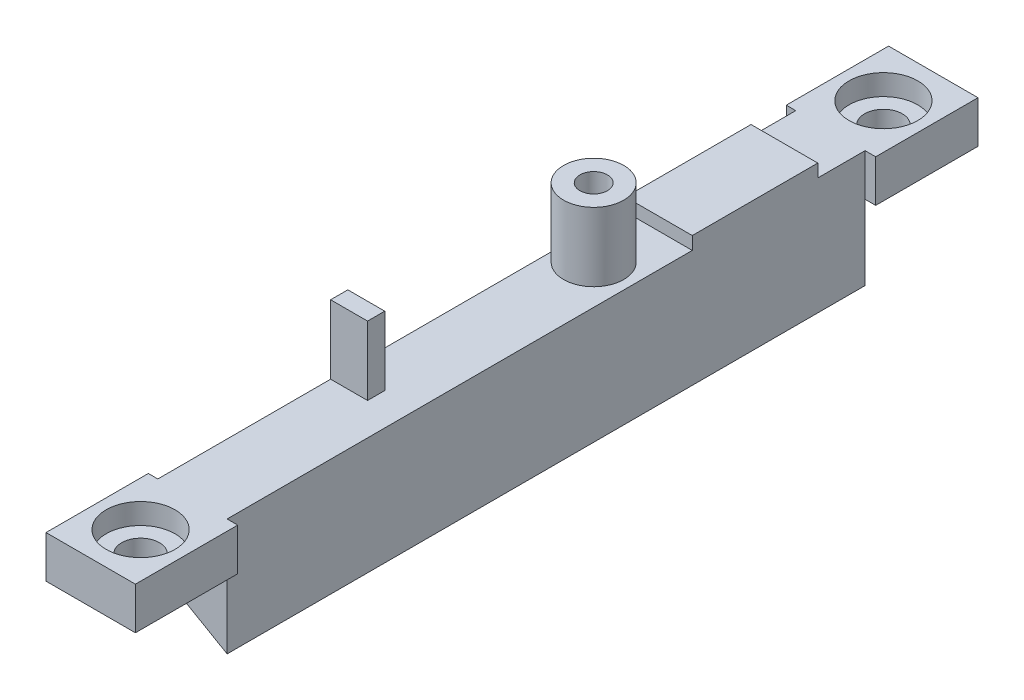
SolidWorks part; units mm, degrees
ref_plane "Front Plane" through (0, 0, 0) normal (0, 0, 1) x (1, 0, 0)
ref_plane "Top Plane" through (0, 0, 0) normal (0, 1, 0) x (1, 0, 0)
ref_plane "Right Plane" through (0, 0, 0) normal (1, 0, 0) x (0, 0, -1)
other "Configuration Table"
sketch "Sketch1" plane through (0, 0, 0) normal (0, 0, 1) x (1, 0, 0)
  line L0 (-17.3973, -4) -> (-13.3671, -4)
  line L1 (-13.3671, -4) -> (-13.3671, -10.7969)
  line L2 (-13.3671, -10.7969) -> (-17.3973, -8.4701)
  line L3 (-17.3973, -8.4701) -> (-17.3973, -4)
extrude "Clamp -X base" add sketch "Sketch1" along normal blind 37.1 from offset 20.15 offset against normal yes
sketch "Sketch2" plane through (0, 0, 0) normal (0, 0, 1) x (1, 0, 0)
  line L0 (-17.95, -6.45) -> (-12.75, -6.45)
  line L1 (-12.75, -6.45) -> (-12.75, -4)
  line L2 (-12.75, -4) -> (-17.95, -4)
  line L3 (-17.95, -4) -> (-17.95, -6.45)
extrude "Ear -X base -26" add sketch "Sketch2" along normal blind 5.95 from offset 26.1 offset against normal yes
sketch "Sketch3" plane through (0, 0, 0) normal (0, 0, 1) x (1, 0, 0)
  line L0 (-17.95, -6.45) -> (-12.75, -6.45)
  line L1 (-12.75, -6.45) -> (-12.75, -4)
  line L2 (-12.75, -4) -> (-17.95, -4)
  line L3 (-17.95, -4) -> (-17.95, -6.45)
extrude "Ear -X base 17" add sketch "Sketch3" along normal blind 5.95 from offset 16.95
sketch "Sketch4" plane through (0, 0, 0) normal (0, 1, 0) x (1, 0, 0)
  circle A0 centre (-15.35, 23.2) radius 1.1
  circle A1 centre (-15.35, -20) radius 1.1
extrude "Cut-Extrude1" cut sketch "Sketch4" along normal blind 2.65 from offset 6.55 offset against normal yes
sketch "Sketch5" plane through (0, 0, 0) normal (0, 1, 0) x (1, 0, 0)
  circle A0 centre (-15.35, 23.2) radius 2
  circle A1 centre (-15.35, -20) radius 2
extrude "Cut-Extrude2" cut sketch "Sketch5" along normal blind 1.22 from offset 5.21 offset against normal yes
sketch "Sketch6" plane through (0, 0, 0) normal (0, 1, 0) x (1, 0, 0)
  line L1 (-17.25, 17.4) -> (-13.3671, 17.4)
  line L2 (-17.25, 17.4) -> (-17.25, 10.1)
  line L3 (-17.25, 10.1) -> (-13.3671, 10.1)
  line L4 (-13.3671, 17.4) -> (-13.3671, 10.1)
extrude "Boss-Extrude4" add sketch "Sketch6" along normal blind 0.75 from offset 4 offset against normal yes
sketch "Sketch7" plane through (0, 0, 0) normal (0, 1, 0) x (1, 0, 0)
  line L1 (-17.3973, -5.9) -> (-15.25, -5.9)
  line L2 (-17.3973, -5.9) -> (-17.3973, -6.9)
  line L3 (-17.3973, -6.9) -> (-15.25, -6.9)
  line L4 (-15.25, -5.9) -> (-15.25, -6.9)
extrude "Boss-Extrude5" add sketch "Sketch7" along normal blind 4 from offset 4 offset against normal yes
sketch "Sketch8" plane through (0, 0, 0) normal (0, 1, 0) x (1, 0, 0)
  circle A0 centre (-15.64, 6.64) radius 1.75
extrude "Boss-Extrude6" add sketch "Sketch8" along normal blind 4 from offset 4 offset against normal yes
sketch "Sketch9" plane through (0, 0, 0) normal (0, 1, 0) x (1, 0, 0)
  circle A0 centre (-15.64, 6.64) radius 0.8
extrude "Cut-Extrude3" cut sketch "Sketch9" along normal blind 5.6 from offset 5.5 offset against normal yes
